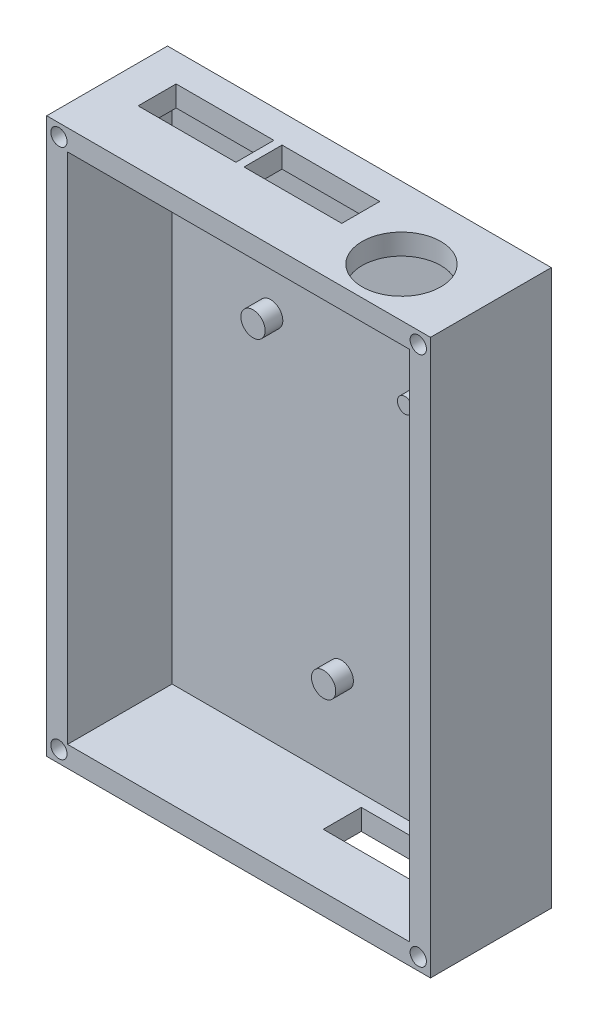
SolidWorks part; units mm, degrees
material "ABS"
ref_plane "Front Plane" through (0, 0, 0) normal (0, 0, 1) x (1, 0, 0)
ref_plane "Top Plane" through (0, 0, 0) normal (0, 1, 0) x (1, 0, 0)
ref_plane "Right Plane" through (0, 0, 0) normal (1, 0, 0) x (0, 0, -1)
sketch "Sketch1" plane through (0, 0, 0) normal (0, 0, 1) x (1, 0, 0)
  line L0 (66.841, 51.091) -> (70.682, 51.091) construction
  line L1 (3.841, 51.091) -> (0, 51.091) construction
  line L2 (35.341, 3.841) -> (35.341, 0) construction
  line L3 (35.341, 98.341) -> (35.341, 102.182) construction
  line L5 (0, 0) -> (70.682, 0)
  line L6 (0, 0) -> (0, 102.182)
  line L7 (0, 102.182) -> (70.682, 102.182)
  line L8 (70.682, 0) -> (70.682, 102.182)
  line L14 (0, 0) -> (1.1893, 1.1893) construction
  line L16 (3.3107, 3.3107) -> (1.1893, 1.1893) construction
  line L17 (0.75, 2.25) -> (0, 2.25) construction
  line L18 (3.841, 3.841) -> (66.841, 3.841)
  line L19 (3.841, 3.841) -> (3.841, 98.341)
  line L20 (3.841, 98.341) -> (66.841, 98.341)
  line L21 (66.841, 3.841) -> (66.841, 98.341)
  line L25 (3.3107, 3.3107) -> (3.841, 3.841)
  circle A0 centre (68.432, 2.25) radius 1.5
  circle A1 centre (2.25, 99.932) radius 1.5
  circle A2 centre (68.432, 99.932) radius 1.5
  circle A3 centre (22, 72) radius 2.2361
  circle A4 centre (35, 21) radius 2.2361
  circle A5 centre (2.25, 2.25) radius 1.5
  circle A6 centre (50, 73) radius 1.4142
  dimension "D17" = 3
  dimension "D2" = 63
  dimension "D3" = 94.5
  dimension "D18" = 0.75
extrude "Boss-Extrude1" add sketch "Sketch1" along normal blind 3.25 contours A3 | A6 | A4 region at (22, 72, 0) region at (35, 21, 0) region at (50, 73, 0)
extrude "Boss-Extrude2" add sketch "Sketch1<21>" against normal blind 3 contours L18 L21 L20 L19 A6 A4 A3 | L5 L8 L7 L6 A2 A0 A5 L19 L20 L21 L18 A1 | A2 | A1 | A3 | A6 | A4 | A5 | A0 region at (1.2425, 51.091, 0) region at (35.3618, 51.0921, 0) region at (2.25, 2.25, 0) region at (68.432, 2.25, 0) region at (2.25, 99.932, 0) region at (68.432, 99.932, 0) region at (22, 72, 0) region at (35, 21, 0) region at (50, 73, 0)
sketch "Sketch1<21>" plane through (0, 0, 0) normal (0, 0, 1) x (1, 0, 0) same geometry as "Sketch1"
extrude "Boss-Extrude4" add sketch "Sketch1<23>" along normal blind 19.25 contours L5 L8 L7 L6 A2 A0 A5 L19 L20 L21 L18 A1 region at (1.2425, 51.091, 0)
sketch "Sketch1<23>" plane through (0, 0, 0) normal (0, 0, 1) x (1, 0, 0) same geometry as "Sketch1"
sketch "Sketch3" plane through (0, 98.341, 0) normal (0, -1, 0) x (1, 0, 0)
  line L0 (3.841, 0) -> (66.841, 0) construction
  line L1 (66.841, 19.25) -> (66.841, 0) construction
  line L2 (3.841, 19.25) -> (3.841, 0) construction
  line L3 (6.841, 2.25) -> (24.841, 2.25)
  line L4 (6.841, 2.25) -> (6.841, 9.25)
  line L5 (6.841, 9.25) -> (24.841, 9.25)
  line L6 (24.841, 2.25) -> (24.841, 9.25)
  line L7 (26.341, 2.25) -> (44.341, 2.25)
  line L8 (26.341, 2.25) -> (26.341, 9.25)
  line L9 (26.341, 9.25) -> (44.341, 9.25)
  line L10 (44.341, 2.25) -> (44.341, 9.25)
  circle A0 centre (56.341, 10.25) radius 7.25
  dimension "D1" = 10.25
  dimension "D3" = 14.5
  dimension "D2" = 10.5
  dimension "D4" = 3
  dimension "D5" = 2.25
  dimension "D6" = 18
  dimension "D7" = 18
  dimension "D8" = 7
  dimension "D9" = 1.5
extrude "Cut-Extrude1" cut sketch "Sketch3" against normal up to surface (3.841 mm away) up to face at (35.341, 102.182, 8.125)
sketch "Sketch4" plane through (0, 0, 0) normal (0, -1, 0) x (1, 0, 0)
  line L0 (0, -3) -> (70.682, -3) construction
  line L1 (40.932, 2.25) -> (58.932, 2.25)
  line L2 (40.932, 2.25) -> (40.932, 9.25)
  line L3 (40.932, 9.25) -> (58.932, 9.25)
  line L4 (58.932, 2.25) -> (58.932, 9.25)
  line L5 (70.682, -3) -> (70.682, 19.25) construction
  dimension "D1" = 18
  dimension "D2" = 7
  dimension "D3" = 5.25
  dimension "D4" = 11.75
extrude "Cut-Extrude2" cut sketch "Sketch4" against normal up to surface (3.841 mm away) up to face at (35.341, 3.841, 9.625)
